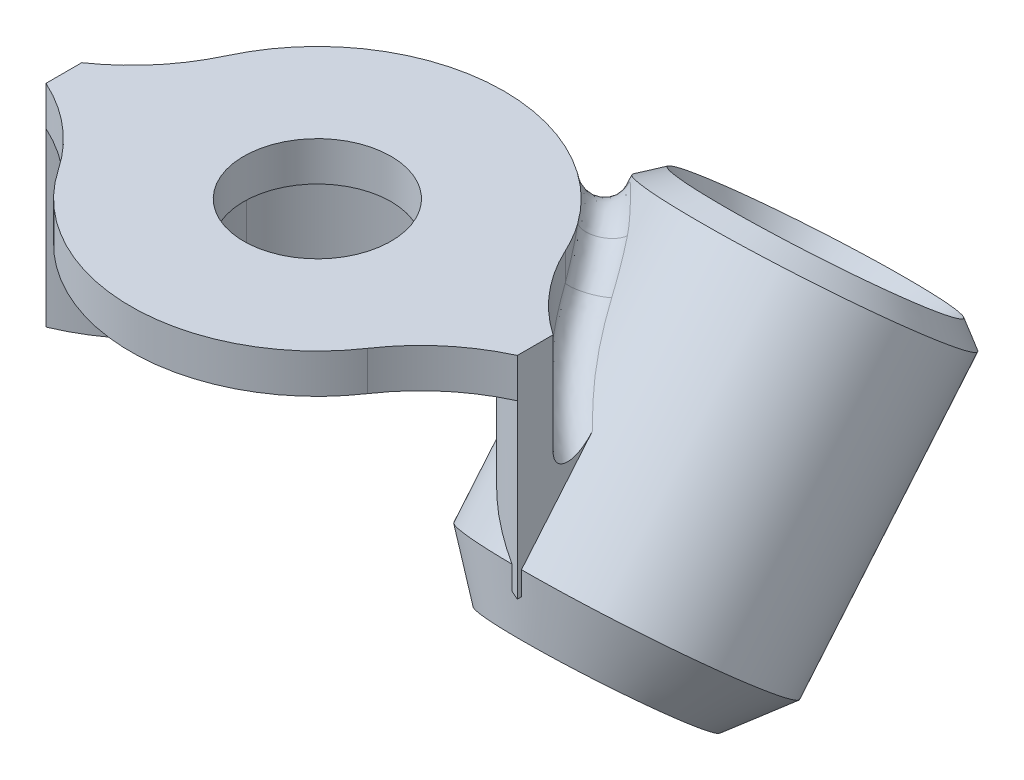
SolidWorks part; units mm, degrees
ref_plane "前视基准面" through (0, 0, 0) normal (0, 0, 1) x (1, 0, 0)
ref_plane "上视基准面" through (0, 0, 0) normal (0, 1, 0) x (1, 0, 0)
ref_plane "右视基准面" through (0, 0, 0) normal (1, 0, 0) x (0, 0, -1)
sketch "草图1" plane through (0, 0, 0) normal (0, 1, 0) x (1, 0, 0)
  line L1 (39.4264, 36.598) -> (16.3284, 13.5)
  line L4 (42.4264, 36.4264) -> (42.4264, 37.9264) construction
  line L5 (41.4264, 36.4264) -> (41.4264, 37.9264)
  line L10 (43.4264, 36.4264) -> (43.4264, 37.9264)
  line L13 (42.4264, 36.4264) -> (42.4264, 37.9264) construction
  line L17 (39.4264, 36.4264) -> (39.4264, 36.598)
  line L24 (45.4264, 36.4264) -> (45.4264, 39.4264)
  line L27 (3.8, 48.8528) -> (4.8, 48.8528)
  line L28 (48.4264, 42.4264) -> (46.9264, 42.4264) construction
  line L31 (48.4264, 39.4264) -> (45.4264, 39.4264)
  line L33 (48.4264, 45.4264) -> (45.4264, 45.4264)
  line L34 (48.4264, 42.4264) -> (46.9264, 42.4264) construction
  line L35 (48.4264, 43.4264) -> (46.9264, 43.4264)
  line L44 (48.4264, 41.4264) -> (46.9264, 41.4264)
  line L45 (42.4264, 48.4264) -> (42.4264, 46.9264) construction
  line L48 (36.4264, 42.4264) -> (37.9264, 42.4264) construction
  line L51 (45.4264, 48.4264) -> (45.4264, 45.4264)
  line L54 (39.4264, 48.4264) -> (39.4264, 45.4264)
  line L57 (36.4264, 45.4264) -> (39.4264, 45.4264)
  line L58 (36.4264, 39.4264) -> (36.598, 39.4264)
  line L59 (42.4264, 48.4264) -> (42.4264, 46.9264) construction
  line L62 (43.4264, 48.4264) -> (43.4264, 46.9264)
  line L63 (41.4264, 48.4264) -> (41.4264, 46.9264)
  line L64 (36.4264, 42.4264) -> (37.9264, 42.4264) construction
  line L65 (36.4264, 41.4264) -> (37.9264, 41.4264)
  line L66 (36.4264, 43.4264) -> (37.9264, 43.4264)
  line L67 (17.1716, 44.229) -> (33.5024, 41.7553)
  line L68 (0, 42) -> (10, 42)
  line L69 (0, 40) -> (10, 40)
  line L70 (0, 1) -> (0, 5)
  line L71 (0, 1) -> (10, 1)
  line L72 (0, -1) -> (10, -1)
  line L73 (-1, 0) -> (-4.9453, 0)
  line L77 (7.5, 5) -> (0, 5)
  line L78 (48.4035, 2.9662) -> (43.7435, 33.731)
  line L84 (36.598, 39.4264) -> (17.1716, 20)
  line L85 (36.4264, -42.4264) -> (37.9264, -42.4264) construction
  line L87 (42.4264, -48.4264) -> (42.4264, -46.9264) construction
  line L88 (48.4264, -42.4264) -> (46.9264, -42.4264) construction
  line L89 (42.4264, -36.4264) -> (42.4264, -37.9264) construction
  line L92 (41.7553, -33.5024) -> (46.5405, -1.9113)
  line L94 (41.7553, 33.5024) -> (46.5405, 1.9113)
  line L95 (17.1716, 20) -> (17.1716, 44.229)
  line L96 (48.4035, -2.9662) -> (43.7435, -33.731)
  line L98 (36.4264, -39.4264) -> (36.598, -39.4264)
  line L99 (36.4264, -45.4264) -> (39.4264, -45.4264)
  line L100 (39.4264, -48.4264) -> (39.4264, -45.4264)
  line L101 (45.4264, -48.4264) -> (45.4264, -45.4264)
  line L102 (48.4264, -45.4264) -> (45.4264, -45.4264)
  line L103 (48.4264, -39.4264) -> (45.4264, -39.4264)
  line L104 (45.4264, -36.4264) -> (45.4264, -39.4264)
  line L105 (39.4264, -36.4264) -> (39.4264, -36.598)
  line L106 (39.4264, -36.598) -> (16.3284, -13.5)
  line L107 (36.4264, -42.4264) -> (37.9264, -42.4264) construction
  line L108 (36.4264, -41.4264) -> (37.9264, -41.4264)
  line L109 (36.4264, -43.4264) -> (37.9264, -43.4264)
  line L110 (42.4264, -48.4264) -> (42.4264, -46.9264) construction
  line L111 (43.4264, -48.4264) -> (43.4264, -46.9264)
  line L112 (41.4264, -48.4264) -> (41.4264, -46.9264)
  line L113 (48.4264, -42.4264) -> (46.9264, -42.4264) construction
  line L114 (48.4264, -43.4264) -> (46.9264, -43.4264)
  line L115 (48.4264, -41.4264) -> (46.9264, -41.4264)
  line L116 (42.4264, -36.4264) -> (42.4264, -37.9264) construction
  line L117 (41.4264, -36.4264) -> (41.4264, -37.9264)
  line L118 (43.4264, -36.4264) -> (43.4264, -37.9264)
  line L119 (33.731, 43.7435) -> (2.9661, 48.4035)
  line L120 (-33.731, 43.7435) -> (-2.9661, 48.4035)
  line L125 (4.8, 48.8528) -> (4.8, 47.3528)
  line L126 (0, -47.3528) -> (0, -44.4131)
  line L127 (0, -51.8528) -> (0, -50.3528)
  line L128 (33.731, -43.7435) -> (2.9661, -48.4035)
  line L129 (17.1716, -44.229) -> (33.5024, -41.7553)
  line L130 (17.1716, -20) -> (17.1716, -44.229)
  line L131 (36.598, -39.4264) -> (17.1716, -20)
  line L132 (36.4264, -39.4264) -> (36.598, -39.4264)
  line L133 (0, -29.3528) -> (10, -29.3528)
  line L135 (10, -43.3528) -> (3, -44.4131)
  line L137 (3, -44.4131) -> (0, -44.4131)
  line L138 (10, -29.3528) -> (10, -43.3528)
  line L139 (0, -29.3528) -> (0, -1)
  line L140 (8.5, 34) -> (8.5, 20) construction
  line L141 (10, 34) -> (10, 20)
  line L142 (7, 34) -> (7, 20)
  line L143 (3.5, 34) -> (3.5, 15) construction
  line L144 (5, 34) -> (5, 15)
  line L145 (2, 34) -> (2, 15)
  line L146 (16.3284, 13.5) -> (16.3284, -13.5)
  line L148 (7.5, 7) -> (0, 7)
  line L149 (0, 7) -> (0, 40)
  line L150 (0, 52.6528) -> (0, 45.0528)
  circle A48 centre (10, 10) radius 1
  circle A49 centre (12.5, 12.5) radius 1
  arc A52 (41.4264, 36.4264) -> (43.4264, 36.4264) centre (42.4264, 36.4264) ccw
  arc A53 (43.4264, 37.9264) -> (41.4264, 37.9264) centre (42.4264, 37.9264) ccw
  arc A54 (39.4264, 36.4264) -> (41.7553, 33.5024) centre (42.4264, 36.4264) ccw
  arc A56 (48.4264, 45.4264) -> (48.4264, 39.4264) centre (48.4264, 42.4264) cw
  arc A57 (48.4264, 43.4264) -> (48.4264, 41.4264) centre (48.4264, 42.4264) cw
  arc A58 (46.9264, 41.4264) -> (46.9264, 43.4264) centre (46.9264, 42.4264) cw
  arc A59 (45.4264, 48.4264) -> (39.4264, 48.4264) centre (42.4264, 48.4264) ccw
  arc A61 (43.4264, 48.4264) -> (41.4264, 48.4264) centre (42.4264, 48.4264) ccw
  arc A62 (41.4264, 46.9264) -> (43.4264, 46.9264) centre (42.4264, 46.9264) ccw
  arc A63 (36.4264, 41.4264) -> (36.4264, 43.4264) centre (36.4264, 42.4264) cw
  arc A64 (37.9264, 43.4264) -> (37.9264, 41.4264) centre (37.9264, 42.4264) cw
  circle A65 centre (42.4264, 42.4264) radius 2.5
  arc A69 (10, 40) -> (10, 42) centre (10, 41) ccw
  arc A71 (10, -1) -> (10, 1) centre (10, 0) ccw
  arc A76 (33.5024, 41.7553) -> (36.4264, 39.4264) centre (36.4264, 42.4264) ccw
  arc A77 (33.5024, -43.0975) -> (36.4264, -45.4264) centre (36.4264, -42.4264) ccw
  arc A80 (2.9661, 48.4035) -> (0, 51.8528) centre (0, 48.8528) ccw
  circle A81 centre (42.4264, -42.4264) radius 2.5
  arc A82 (36.4264, -39.4264) -> (33.731, -41.1093) centre (36.4264, -42.4264) ccw
  arc A83 (45.4264, -48.4264) -> (39.4264, -48.4264) centre (42.4264, -48.4264) cw
  arc A84 (48.4264, -45.4264) -> (48.4264, -39.4264) centre (48.4264, -42.4264) ccw
  arc A85 (39.4264, -36.4264) -> (41.7553, -33.5024) centre (42.4264, -36.4264) cw
  circle A86 centre (12.5, -12.5) radius 1
  circle A87 centre (10, -10) radius 1
  arc A88 (36.4264, -41.4264) -> (36.4264, -43.4264) centre (36.4264, -42.4264) ccw
  arc A89 (37.9264, -43.4264) -> (37.9264, -41.4264) centre (37.9264, -42.4264) ccw
  arc A90 (43.4264, -48.4264) -> (41.4264, -48.4264) centre (42.4264, -48.4264) cw
  arc A91 (41.4264, -46.9264) -> (43.4264, -46.9264) centre (42.4264, -46.9264) cw
  arc A92 (48.4264, -43.4264) -> (48.4264, -41.4264) centre (48.4264, -42.4264) ccw
  arc A93 (46.9264, -41.4264) -> (46.9264, -43.4264) centre (46.9264, -42.4264) ccw
  arc A94 (41.4264, -36.4264) -> (43.4264, -36.4264) centre (42.4264, -36.4264) cw
  arc A95 (43.4264, -37.9264) -> (41.4264, -37.9264) centre (42.4264, -37.9264) cw
  circle A99 centre (48.8528, 0) radius 1.5
  arc A101 (48.4035, -2.9662) -> (48.4035, 2.9662) centre (48.8528, 0) ccw
  arc A102 (43.7435, 33.731) -> (45.4264, 36.4264) centre (42.4264, 36.4264) ccw
  arc A103 (46.5405, 1.9113) -> (46.5405, -1.9113) centre (48.8528, 0) ccw
  arc A104 (43.7435, -33.731) -> (45.4264, -36.4264) centre (42.4264, -36.4264) cw
  arc A105 (36.4264, 45.4264) -> (33.731, 43.7435) centre (36.4264, 42.4264) ccw
  arc A106 (2.9661, -48.4035) -> (0, -51.8528) centre (0, -48.8528) cw
  arc A107 (0, -50.3528) -> (0, -47.3528) centre (0, -48.8528) ccw
  arc A108 (33.5024, -41.7553) -> (36.4264, -39.4264) centre (36.4264, -42.4264) cw
  circle A109 centre (10, -26.3528) radius 1.5
  arc A110 (10, 34) -> (7, 34) centre (8.5, 34) ccw
  arc A111 (7, 20) -> (10, 20) centre (8.5, 20) ccw
  arc A112 (5, 34) -> (2, 34) centre (3.5, 34) ccw
  arc A113 (2, 15) -> (5, 15) centre (3.5, 15) ccw
  arc A114 (7.5, 5) -> (7.5, 7) centre (7.5, 6) ccw
  circle A115 centre (0, 48.8528) radius 3.8
  circle A116 centre (0, 48.8528) radius 1.5
  circle A117 centre (0, 48.8528) radius 3
  point P0 (8.5, 27)
  point P11 (42.4264, 37.1764)
  point P16 (42.4264, 37.1764)
  point P28 (47.6764, 42.4264)
  point P29 (47.6764, 42.4264)
  point P44 (5, 30)
  point P47 (42.4264, 47.6764)
  point P48 (37.1764, 42.4264)
  point P49 (42.4264, 47.6764)
  point P54 (37.1764, 42.4264)
  point P63 (5, 0)
  point P118 (15.3284, 0)
  point P127 (37.1764, -42.4264)
  point P134 (42.4264, -47.6764)
  point P139 (47.6764, -42.4264)
  point P144 (42.4264, -37.1764)
  point P145 (42.4264, -37.1764)
  point P166 (3.75, 4)
  point P167 (3.5, 24.5)
extrude "凸台-拉伸1" add sketch "草图1" along normal blind 4.3 contours L119 A115 L150 A80 | A115 L119 L125 L27 | L150 A117 A80 A116 | A117 L150 A115 L119 region at (2.2818, 0, -50.815) region at (4.3127, 0, -48.5244) region at (2.0445, 0, -46.4753) region at (2.0739, 0, -50.9267)
extrude "切除-拉伸1" cut sketch "草图1<8>" along normal blind 3.5 contours L150 A117 A80 A116 | A117 L150 A115 L119 region at (2.0445, 0, -46.4753) region at (2.0739, 0, -50.9267)
sketch "草图1<8>" plane through (0, 0, 0) normal (0, 1, 0) x (1, 0, 0) same geometry as "草图1"
mirror "镜向1" about plane through (0, 4.3, 0) normal (1, 0, 0) of bodies 118 109
fillet "圆角2" radius 4 4 edges at (3.8, 2.15, -48.8528) (-3.8, 2.15, -48.8528) (2.9661, 1.75, -48.4035) (-2.9661, 1.75, -48.4035)
fillet "圆角4" radius 4 2 edges at (-3.798, 3.9, -48.7296) (3.798, 3.9, -48.7296)
sketch "草图2" plane through (4.8, 0, 0) normal (1, 0, 0) x (0, 0, -1)
  line L3 (49.7421, -2.0516) -> (54.8844, 4.0767)
  line L12 (48.21, -0.766) -> (52.3583, 4.1777)
  line L13 (48.21, -0.766) -> (48.21, 0.4785)
  line L14 (51.8362, 4.8) -> (52.3583, 4.8)
  line L15 (51.8362, 4.8) -> (48.21, 0.4785)
  line L16 (52.3583, 4.8) -> (52.3583, 4.1777)
revolve "旋转1" add sketch "草图2" angle 360 about L3 region at (4.8, -0.2553, -48.4243) region at (4.8, 2.3703, -50.3156)
fillet "圆角3" radius 0.4 2 edges at (2.6877, 2.9494, -51.5391) (4.3564, 1.6126, -49.2078)
